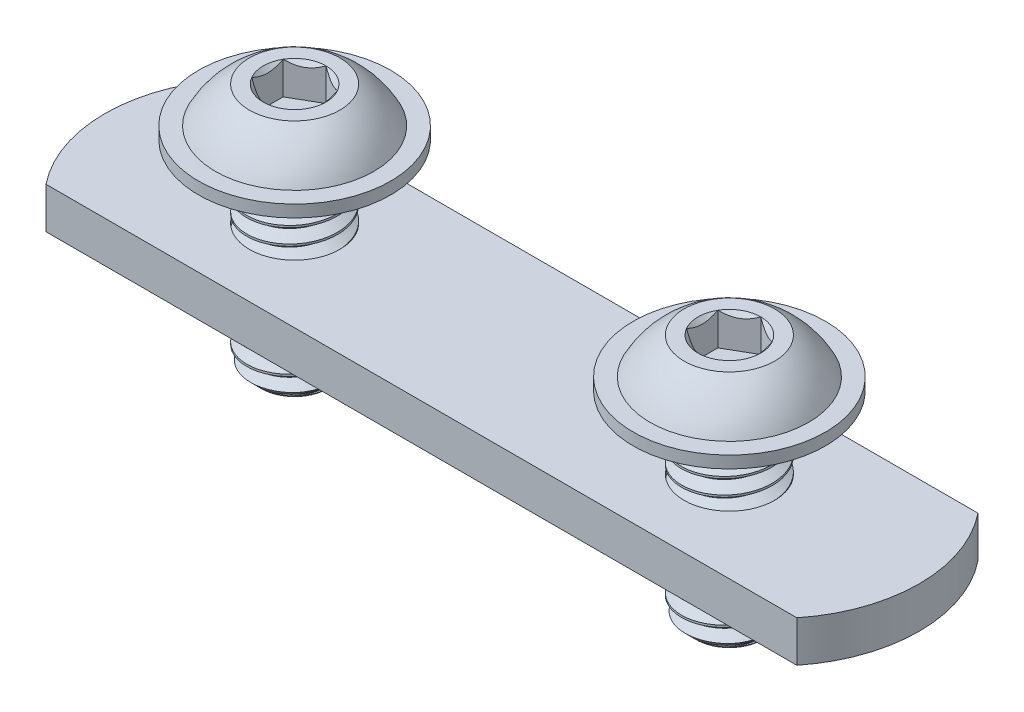
SolidWorks part; units mm, degrees
ref_plane "Front Plane" through (0, 0, 0) normal (0, 0, 1) x (1, 0, 0)
ref_plane "Top Plane" through (0, 0, 0) normal (0, 1, 0) x (1, 0, 0)
ref_plane "Right Plane" through (0, 0, 0) normal (1, 0, 0) x (0, 0, -1)
sketch "Sketch1" plane through (0, 0, 0) normal (0, 1, 0) x (1, 0, 0)
  line L0 (-19.05, 0) -> (19.05, 0) construction
  circle A0 centre (-19.05, 0) radius 3.9688
  point P3 (-23.0188, 0)
  point P4 (-15.0813, 0)
  dimension "D1" = 7.9375
  dimension "D2" = 38.1
extrude "Boss-Extrude1" add sketch "Sketch1" against normal blind 17.4625
sketch "Sketch2" plane through (0, -17.4625, 0) normal (0, -1, 0) x (1, 0, 0)
  circle A1 centre (-19.05, 0) radius 3.9688
  circle A2 centre (-19.05, 0) radius 3.9688
  point P0 (-19.05, -3.9688)
  dimension "D1" = 0
curve "Helix/Spiral1" pitch 1.4111 height 18.8736 turns 13.375
ref_plane "Plane1" through (-19.05, 0, 0) normal (1, 0, 0) x (0, 0, -1)
sketch "Sketch3" plane through (-19.05, 0, 0) normal (1, 0, 0) x (0, 0, -1)
  line L0 (4.1215, -17.3743) -> (2.8994, -18.0799) construction
  line L1 (2.8994, -18.0799) -> (4.1215, -18.7854) construction
  line L2 (4.1215, -18.7854) -> (4.1215, -17.3743) construction
  line L3 (3.0522, -17.9917) -> (3.0522, -18.1681) construction
  line L4 (3.9688, -17.4625) -> (3.9688, -18.6972) construction
  line L5 (2.8994, -18.0799) -> (3.0522, -18.0799) construction
  line L6 (3.9688, -18.0799) -> (4.1215, -18.0799) construction
  line L8 (2.8994, -18.0799) -> (-3.9688, -18.0799) construction
  line L9 (3.0522, -17.9917) -> (4.0451, -17.4184)
  line L10 (3.0522, -17.9917) -> (3.0522, -18.1681)
  line L11 (3.0522, -18.1681) -> (4.0451, -18.7413)
  line L12 (4.0451, -18.7413) -> (4.0451, -17.4184)
  line L14 (-3.9688, -18.0799) -> (-3.9688, -16.6687) construction
  line L15 (-3.9688, -16.6687) -> (-3.9688, -15.2576) construction
  line L16 (-3.9688, -15.2576) -> (-3.9687, -13.8465) construction
  line L17 (-3.9687, -13.8465) -> (-3.9688, -12.4354) construction
  line L18 (-3.9688, 0) -> (-3.9688, -17.4625) construction
  point P15 (4.0451, -18.0799)
  dimension "D1" = 1.4111
  dimension "D2" = 0.1764
sweep "Cut-Sweep1" cut profiles "Sketch3" path "Helix/Spiral1" align with end faces yes
sketch "Sketch4" plane through (0, -17.4625, 0) normal (0, -1, 0) x (1, 0, 0)
  circle A0 centre (-19.05, 0) radius 2.8994
extrude "Cut-Extrude1" cut sketch "Sketch4" against normal blind 1.4111 draft 45 flip side to cut
sketch "Sketch5" plane through (0, 0, 0) normal (0, 0, 1) x (1, 0, 0)
  line L0 (-19.05, 0) -> (-19.05, 4.2164)
  line L1 (-27.4701, 0) -> (-19.05, 0)
  line L2 (-19.05, 4.2164) -> (-23.0188, 4.2164)
  line L3 (-25.9969, 1.0541) -> (-27.4701, 1.0541)
  line L4 (-27.4701, 1.0541) -> (-27.4701, 0)
  line L5 (-19.05, 0) -> (-19.05, -17.4625) construction
  arc A0 (-23.0188, 4.2164) -> (-25.9969, 1.0541) centre (-19.05, -2.5047) ccw
  dimension "D1" = 4.2164
  dimension "D2" = 1.0541
  dimension "D3" = 16.8402
  dimension "D4" = 13.8938
revolve "Revolve1" add sketch "Sketch5" angle 360 mid plane about L0
sketch "Sketch6" plane through (0, 4.2164, 0) normal (0, 1, 0) x (1, 0, 0)
  line L1 (-19.05, 2.7496) -> (-21.4313, 1.3748)
  line L2 (-21.4313, 1.3748) -> (-21.4312, -1.3748)
  line L3 (-21.4312, -1.3748) -> (-19.05, -2.7496)
  line L4 (-19.05, -2.7496) -> (-16.6688, -1.3748)
  line L5 (-16.6688, -1.3748) -> (-16.6688, 1.3748)
  line L6 (-16.6688, 1.3748) -> (-19.05, 2.7496)
  circle A0 centre (-19.05, 0) radius 2.3813 construction
  dimension "D1" = 4.7625
extrude "Cut-Extrude2" cut sketch "Sketch6" against normal blind 2.8575
sketch "Sketch7" plane through (0, 4.2164, 0) normal (0, 1, 0) x (1, 0, 0)
  circle A0 centre (-19.05, 0) radius 2.7496
extrude "Cut-Extrude3" cut sketch "Sketch7" against normal blind 2.8575 draft 45
move or copy body "Body-Move/Copy1" bodies to move or copy 110 copy yes number of copies 1 translate (38.1, 0, 0)
sketch "Sketch8" plane through (0, 0, 0) normal (0, 1, 0) x (1, 0, 0)
  line L0 (-35.687, 0) -> (35.687, 0) construction
  line L2 (-32.9009, 7.9375) -> (32.9009, 7.9375)
  line L3 (-32.9009, -7.9375) -> (32.9009, -7.9375)
  line L4 (-35.687, 7.9375) -> (35.687, 7.9375) construction
  line L5 (-35.687, 7.9375) -> (-35.687, -7.9375) construction
  line L6 (-35.687, -7.9375) -> (35.687, -7.9375) construction
  line L7 (35.687, 7.9375) -> (35.687, -7.9375) construction
  arc A0 (-32.9009, 7.9375) -> (-32.9009, -7.9375) centre (-22.987, 0) ccw
  arc A1 (32.9009, 7.9375) -> (32.9009, -7.9375) centre (22.987, 0) cw
  circle A2 centre (19.05, 0) radius 3.9688
  circle A3 centre (-19.05, 0) radius 3.9688
  circle A4 centre (-19.05, 0) radius 3.9688
  dimension "D2" = 71.374
  dimension "D6" = 12.7
  dimension "D3" = 15.875
  dimension "D4" = 16.637
  dimension "D1" = 0
extrude "Boss-Extrude2" add sketch "Sketch8" against normal blind 3.6068 from offset 6.35 separate body offset against normal yes
sketch "Sketch9" plane through (0, -9.9568, 0) normal (0, -1, 0) x (1, 0, 0)
  circle A0 centre (19.05, 0) radius 3.9688 construction
  circle A1 centre (-19.05, 0) radius 3.9688 construction
  circle A2 centre (-19.05, 0) radius 3.9688
  circle A3 centre (-19.05, 0) radius 4.5593
  circle A4 centre (19.05, 0) radius 3.9688
  circle A5 centre (19.05, 0) radius 4.5593
  dimension "D1" = 9.1186
extrude "Boss-Extrude3" add sketch "Sketch9" along normal blind 2.032
sketch "SketchZ" plane through (0, 0, 0) normal (0, 0, 1) x (1, 0, 0)
  line L0 (-15.0813, -17.7271) -> (-15.0813, -16.316) construction
  line L2 (-19.05, -18.0799) -> (-19.05, -16.6687) construction
  line L4 (-15.0813, -17.7271) -> (-19.05, -17.7271) construction
  line L5 (-19.05, -13.8465) -> (-19.05, -12.4354) construction
  line L6 (-19.05, -17.3743) -> (-19.05, -18.0799) construction
equation "\"D3@Helix/Spiral1\" = \"D4@Helix/Spiral1\" + \"D1@Boss-Extrude1\""
equation "\"D1@Sketch3\" = \"D4@Helix/Spiral1\""
equation "\"D2@Sketch3\" = \"D1@Sketch3\" / 8"
equation "\"D1@Cut-Extrude1\" = \"D4@Helix/Spiral1\""
equation "\"D1@Cut-Extrude2\" = \"D1@Sketch6\" * 3/5"
equation "\"D1@Cut-Extrude3\" = \"D1@Cut-Extrude2\""
equation "\"D2@Sketch5\" = \"D1@Sketch5\" * 1/4"
